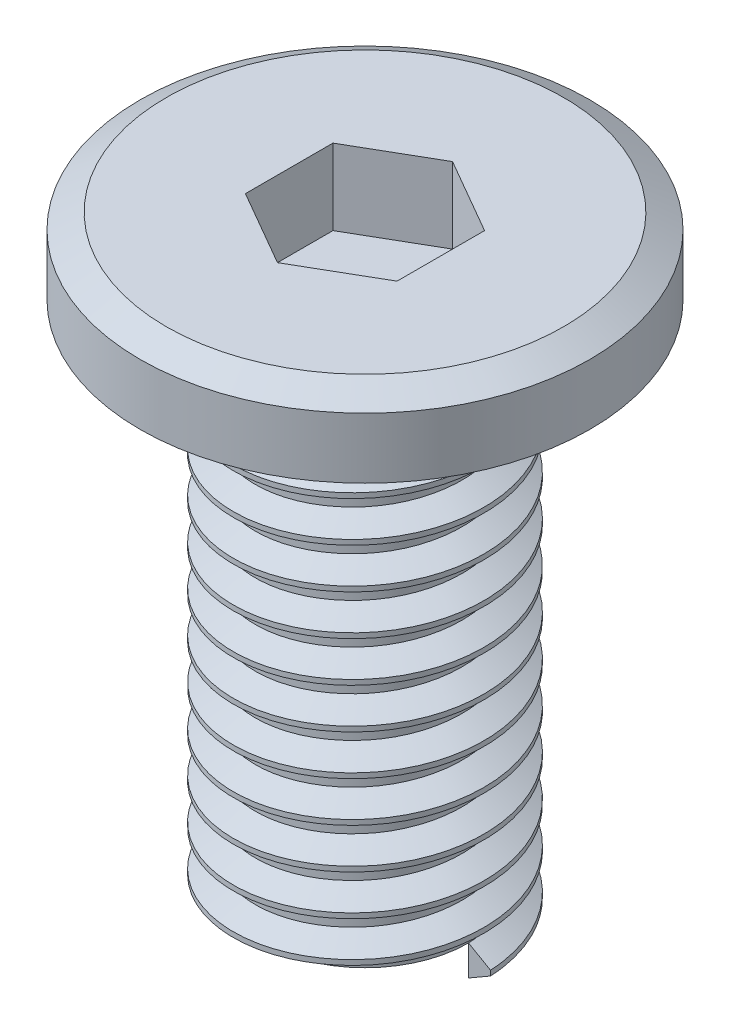
SolidWorks part; units mm, degrees
ref_plane "Front Plane" through (0, 0, 0) normal (0, 0, 1) x (1, 0, 0)
ref_plane "Top Plane" through (0, 0, 0) normal (0, 1, 0) x (1, 0, 0)
ref_plane "Right Plane" through (0, 0, 0) normal (1, 0, 0) x (0, 0, -1)
sketch "Sketch1" plane through (0, 0, 0) normal (0, 1, 0) x (1, 0, 0)
  circle A0 centre (0, 0) radius 4.45
  dimension "D1" = 8.9
extrude "Boss-Extrude1" add sketch "Sketch1" along normal blind 1.5
chamfer "Chamfer2" distance 0.3 angle 60 1 edges at (0, 1.5, 4.45) first distance on face at (0, 1.5, 4.45)
sketch "Sketch8" plane through (0, 1.5, 0) normal (0, 1, 0) x (1, 0, 0)
  line L1 (0, 1.7321) -> (-1.5, 0.866)
  line L2 (-1.5, 0.866) -> (-1.5, -0.866)
  line L3 (-1.5, -0.866) -> (0, -1.7321)
  line L4 (0, -1.7321) -> (1.5, -0.866)
  line L5 (1.5, -0.866) -> (1.5, 0.866)
  line L6 (1.5, 0.866) -> (0, 1.7321)
  circle A0 centre (0, 0) radius 1.5 construction
  dimension "D1" = 3
  dimension "D2" = 1.5
extrude "Cut-Extrude1" cut sketch "Sketch8" against normal blind 3
sketch "Sketch3" plane through (0, 0, 0) normal (0, -1, 0) x (1, 0, 0)
  circle A0 centre (0, 0) radius 2.05
  dimension "D1" = 4.1
extrude "Boss-Extrude2" add sketch "Sketch3" along normal blind 10
thread "Thread1" pitch 0.8 method extrude profile "Thread Profile2" start angle 0, offset 0, length 0, pitch 0.8, diameter 4.1
ref_plane "Plane2" through (-2.05, 0, 0) normal (0, 0, 1) x (-1, 0, 0)
sketch "Thread Profile2" plane through (-2.05, 0, 0) normal (0, 0, 1) x (-1, 0, 0)
  line L0 (0, 0) -> (0, 0.8) construction
  line L1 (0, 0) -> (0.433, 0.25)
  line L2 (0.433, 0.25) -> (0.433, 0.35)
  line L3 (0.433, 0.35) -> (0, 0.6)
  line L4 (0.433, 0.3) -> (0, 0.3) construction
  line L11 (0, 0) -> (0, 0.6)
  point P2 (0, 0)
  dimension "Pitch" = 0.8
  dimension "Profile_Angle" = 60
  dimension "Profile_Land" = 0.1
  dimension "Profile_Height" = 0.433
